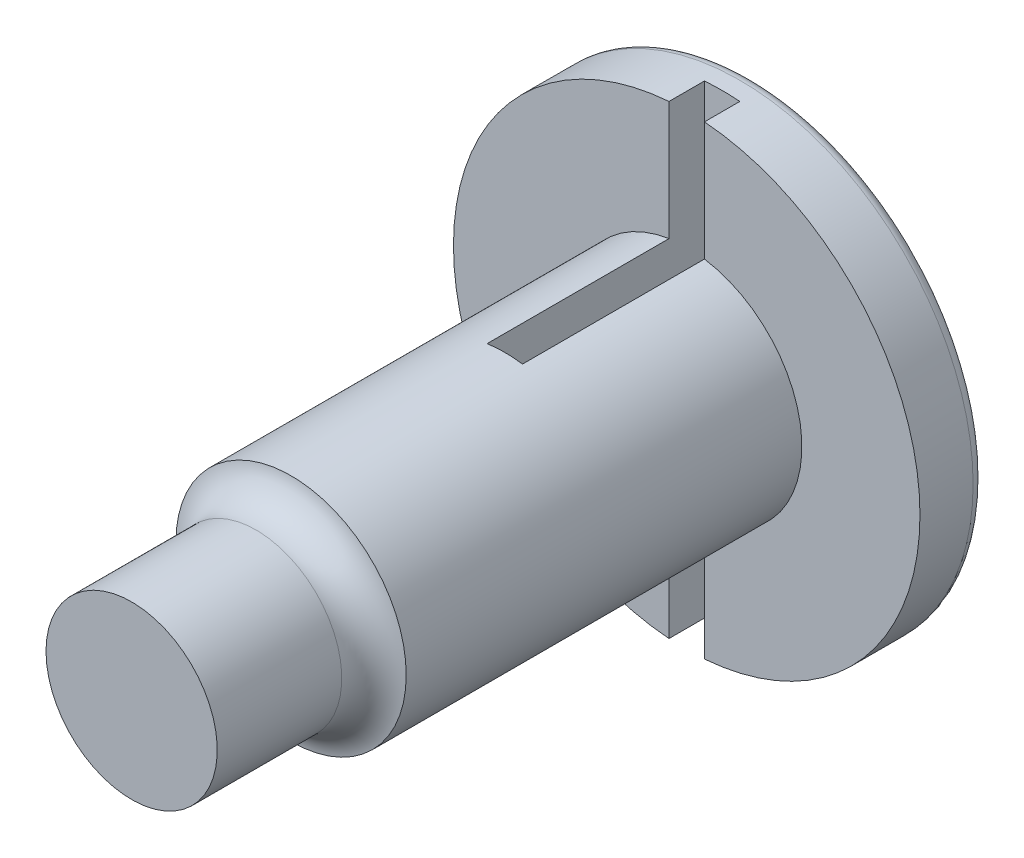
SolidWorks part; units mm, degrees
ref_plane "Front Plane" through (0, 0, 0) normal (0, 0, 1) x (1, 0, 0)
ref_plane "Top Plane" through (0, 0, 0) normal (0, 1, 0) x (1, 0, 0)
ref_plane "Right Plane" through (0, 0, 0) normal (1, 0, 0) x (0, 0, -1)
sketch "Sketch1" plane through (0, 0, 0) normal (0, 0, 1) x (1, 0, 0)
  circle A0 centre (0, 0) radius 197.5
extrude "Boss-Extrude1" add sketch "Sketch1" against normal blind 55
sketch "Sketch2" plane through (0, 0, 0) normal (0, 0, 1) x (1, 0, 0)
  circle A0 centre (0, 0) radius 97.5
extrude "Boss-Extrude2" add sketch "Sketch2" along normal blind 335
sketch "Sketch3" plane through (0, 0, 0) normal (0, 0, 1) x (1, 0, 0)
  circle A0 centre (0, 0) radius 72.5
extrude "Boss-Extrude3" add sketch "Sketch3" along normal blind 470
sketch "Sketch4" plane through (0, 0, 0) normal (0, 0, 1) x (1, 0, 0)
  line L0 (0, 0) -> (0, 197.5) construction
  line L1 (0, 197.5) -> (-15, 197.5)
  line L2 (0, 0) -> (0, -197.5) construction
  line L3 (-15, 197.5) -> (-15, -197.5)
  line L4 (-15, -197.5) -> (0, -197.5)
  line L5 (0, -197.5) -> (15, -197.5)
  line L6 (15, -197.5) -> (15, 197.5)
  line L7 (15, 197.5) -> (0, 197.5)
  circle A0 centre (0, 0) radius 197.5 construction
  dimension "D1" = 15
extrude "Cut-Extrude1" cut sketch "Sketch4" against normal blind 30
sketch "Sketch7" plane through (0, 0, 0) normal (1, 0, 0) x (0, 0, -1)
  line L0 (0, 0) -> (0, 273)
  line L1 (0, 273) -> (-161.375, 273)
  line L3 (-138.625, -273) -> (0, -273)
  line L4 (0, -273) -> (0, 0)
  line L5 (-138.625, -273) -> (-161.375, 273)
  dimension "D1" = 273
  dimension "D2" = 138.625
  dimension "D3" = 161.375
extrude "Cut-Extrude2" cut sketch "Sketch7" against normal blind 15 and the other way blind 15
sketch "Sketch8" plane through (0, 0, 0) normal (0, 0, 1) x (1, 0, 0)
  circle A0 centre (0, 0) radius 57.5
extrude "Cut-Extrude3" cut sketch "Sketch8" along normal blind 235 and the other way blind 285
fillet "Fillet1" radius 30 1 edges at (72.5, 0, 335)
fillet "Fillet2" radius 10 1 edges at (197.5, 0, -55)
